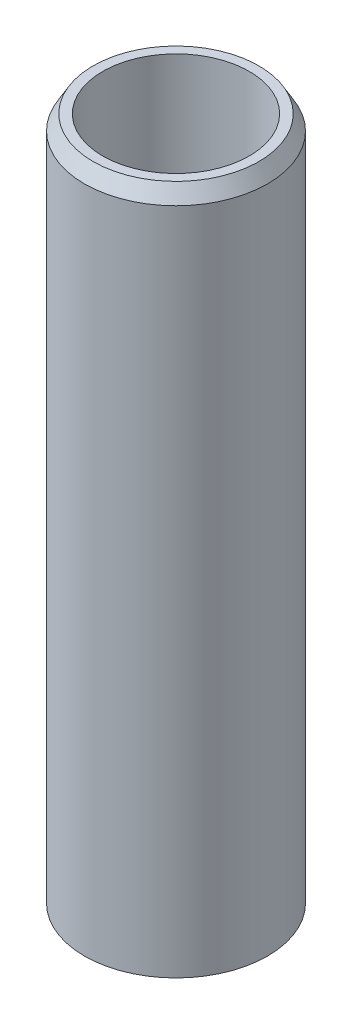
SolidWorks part; units mm, degrees
ref_plane "Front Plane" through (0, 0, 0) normal (0, 0, 1) x (1, 0, 0)
ref_plane "Top Plane" through (0, 0, 0) normal (0, 1, 0) x (1, 0, 0)
ref_plane "Right Plane" through (0, 0, 0) normal (1, 0, 0) x (0, 0, -1)
sketch "Sketch1" plane through (0, 0, 0) normal (0, 1, 0) x (1, 0, 0)
  circle A0 centre (0, 0) radius 25
  dimension "SHAFT_OD" = 50
extrude "Boss-Extrude1" add sketch "Sketch1" along normal blind 189.0217
sketch "Sketch2" plane through (0, 0, 0) normal (0, 1, 0) x (1, 0, 0)
  circle A0 centre (0, 0) radius 20.0127
  dimension "BORE_D" = 40.0255
extrude "Cut-Extrude1" cut sketch "Sketch2" along normal through all
chamfer "Chamfer1" distance 4.0938 angle 30 2 edges at (0, 189.0217, 25) (0, 0, 25) first distance on face at (0, 189.0217, 25) first distance on face at (0, 0, 20.0127)
